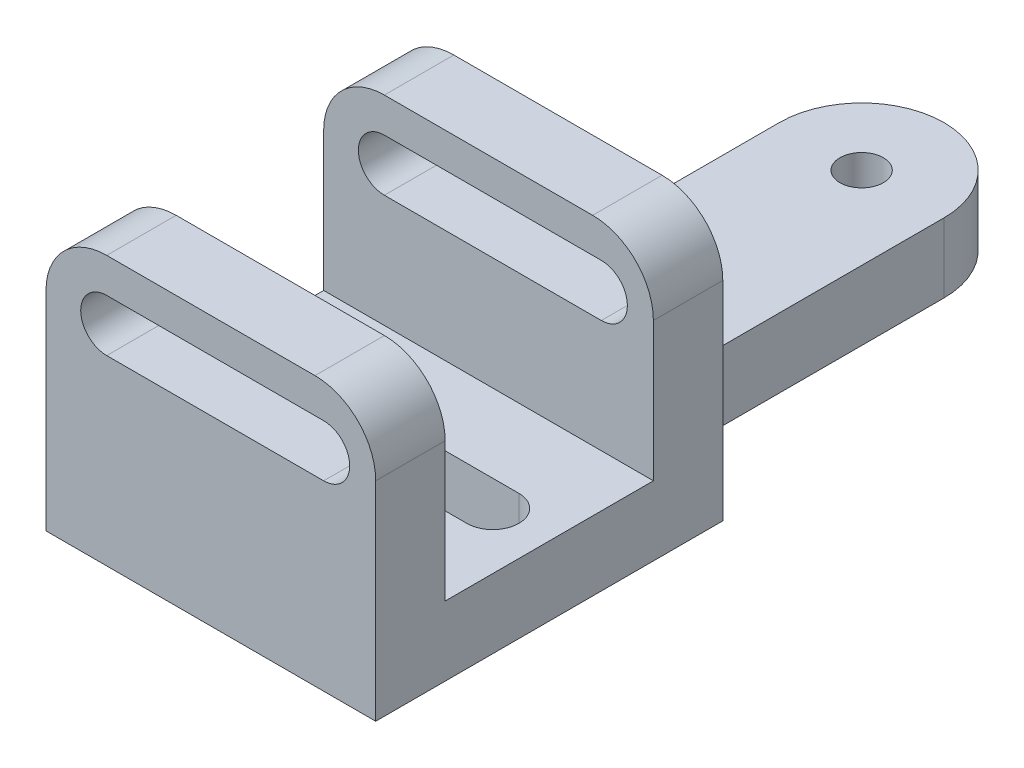
SolidWorks part; units mm, degrees
ref_plane "Piano frontale" through (0, 0, 0) normal (0, 0, 1) x (1, 0, 0)
ref_plane "Piano superiore" through (0, 0, 0) normal (0, 1, 0) x (1, 0, 0)
ref_plane "Piano destro" through (0, 0, 0) normal (1, 0, 0) x (0, 0, -1)
sketch "Schizzo2" plane through (0, 0, 0) normal (1, 0, 0) x (0, 0, -1)
  line L0 (0, 62) -> (0, 0)
  line L1 (0, 0) -> (80, 0)
  line L2 (80, 0) -> (80, 62)
  line L3 (80, 62) -> (64, 62)
  line L4 (64, 62) -> (64, 16)
  line L5 (64, 16) -> (16, 16)
  line L6 (16, 16) -> (16, 62)
  line L7 (16, 62) -> (0, 62)
  dimension "D1" = 80
  dimension "D2" = 16
  dimension "D3" = 16
  dimension "D4" = 62
  dimension "D5" = 62
  dimension "D6" = 16
extrude "Estrusione-Estrusione1" add sketch "Schizzo2" along normal mid plane 76
sketch "Schizzo3" plane through (0, 0, 0) normal (0, -1, 0) x (1, 0, 0)
  line L0 (0, 0) -> (0, -178.6371) construction
  line L1 (-19, -80) -> (-19, -169)
  line L2 (38, -80) -> (-38, -80) construction
  line L3 (-19, -169) -> (19, -169)
  line L4 (-19, -80) -> (19, -80)
  line L5 (19, -80) -> (19, -169)
  point P7 (0, -178.6371)
  point P11 (0, -169)
  point P12 (0, -80)
  dimension "D1" = 89
  dimension "D2" = 38
extrude "Estrusione-Estrusione2" add sketch "Schizzo3" against normal blind 16
fillet "Raccordo1" radius 19 2 edges at (19, 8, -169) (-19, 8, -169)
fillet "Raccordo2" radius 14 4 edges at (-38, 62, -72) (-38, 62, -8) (38, 62, -72) (38, 62, -8)
sketch "Schizzo4" plane through (0, 16, 0) normal (0, 1, 0) x (1, 0, 0)
  line L0 (25, 16) -> (25, 40) construction
  line L1 (38, 16) -> (-38, 16) construction
  line L2 (25, 40) -> (-25, 40) construction
  line L3 (25, 34) -> (-25, 34)
  line L4 (25, 46) -> (-25, 46)
  line L5 (38, 64) -> (38, 16) construction
  arc A0 (25, 34) -> (25, 46) centre (25, 40) ccw
  arc A1 (-25, 46) -> (-25, 34) centre (-25, 40) ccw
  point P4 (0, 40)
  dimension "D4" = 6
  dimension "D1" = 24
  dimension "D2" = 50
  dimension "D3" = 13
extrude "Taglio-Estrusione1" cut sketch "Schizzo4" against normal up to next
sketch "Schizzo5" plane through (0, 0, 0) normal (0, 0, 1) x (1, 0, 0)
  line L0 (-24, 62) -> (-24, 48) construction
  line L1 (-24, 48) -> (26, 48) construction
  line L2 (-24, 54) -> (26, 54)
  line L3 (-24, 42) -> (26, 42)
  arc A0 (-24, 54) -> (-24, 42) centre (-24, 48) ccw
  arc A1 (26, 42) -> (26, 54) centre (26, 48) ccw
  point P3 (1, 48)
  dimension "D3" = 6
  dimension "D1" = 14
  dimension "D2" = 50
extrude "Taglio-Estrusione2" cut sketch "Schizzo5" against normal through all
hole_wizard "Foro Ø10.0 (10)-2" positions "Schizzo6" profile "Schizzo7" hole size "Ø10.0" standard "ISO" end condition up to next
sketch "Schizzo6" plane through (0, 16, 0) normal (0, 1, 0) x (1, 0, 0)
  line L0 (0, 80) -> (0, 150) construction
  line L1 (19, 80) -> (-19, 80) construction
  point P2 (0, 150)
  dimension "D1" = 70
sketch "Schizzo7" plane through (0, 16, -150) normal (1, 0, 0) x (0, 0, 1)
  line L0 (0, 0) -> (0, 16)
  line L1 (0, 16) -> (5, 16)
  line L2 (5, 16) -> (5, 0)
  line L5 (5, 0) -> (0, 0)
  line L11 (0, -6.35) -> (0, 107.95) construction
  dimension "Thru Hole Dia." = 10
  dimension "Thru Hole Depth" = 16
fillet "Raccordo3" radius 14 2 edges at (-19, 8, -80) (19, 8, -80)
